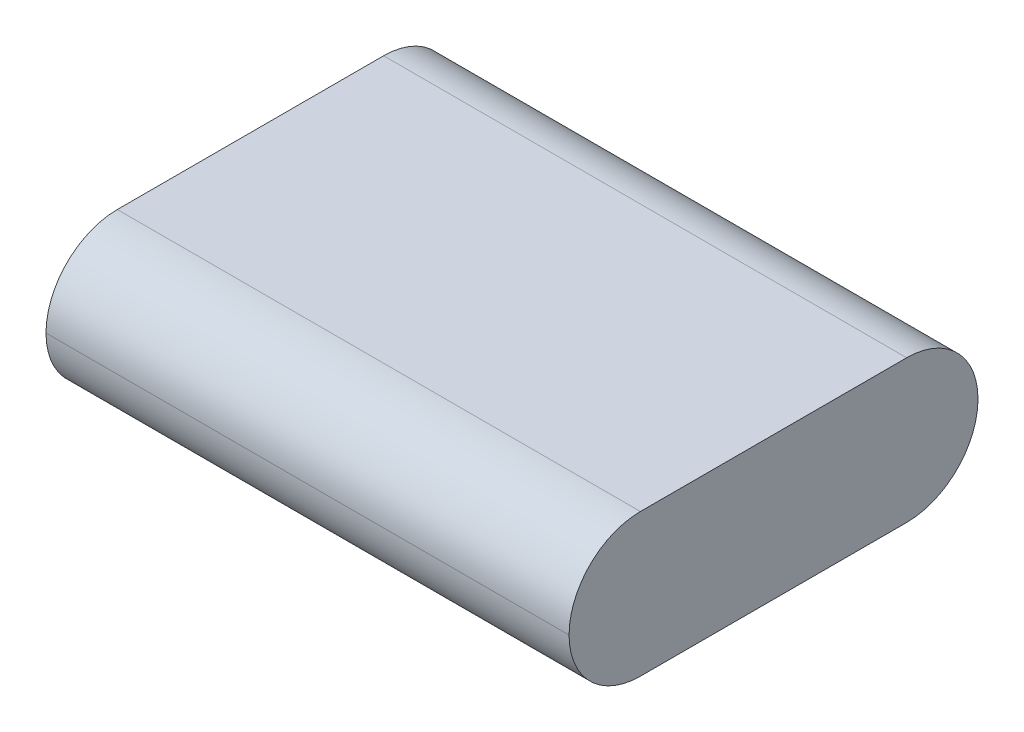
SolidWorks part; units mm, degrees
ref_plane "Front Plane" through (0, 0, 0) normal (0, 0, 1) x (1, 0, 0)
ref_plane "Top Plane" through (0, 0, 0) normal (0, 1, 0) x (1, 0, 0)
ref_plane "Right Plane" through (0, 0, 0) normal (1, 0, 0) x (0, 0, -1)
sketch "Sketch1" plane through (0, 0, 0) normal (0, 1, 0) x (1, 0, 0)
  line L1 (-34.925, 54.61) -> (34.925, 54.61)
  line L2 (-34.925, 54.61) -> (-34.925, 0)
  line L3 (-34.925, 0) -> (34.925, 0)
  line L4 (34.925, 54.61) -> (34.925, 0)
  dimension "D1" = 69.85
  dimension "D2" = 54.61
extrude "Boss-Extrude1" add sketch "Sketch1" along normal blind 19.05
fillet "Fillet1" radius 9.525 4 edges at (0, 0, -54.61) (0, 19.05, -54.61) (0, 0, 0) (0, 19.05, 0)
